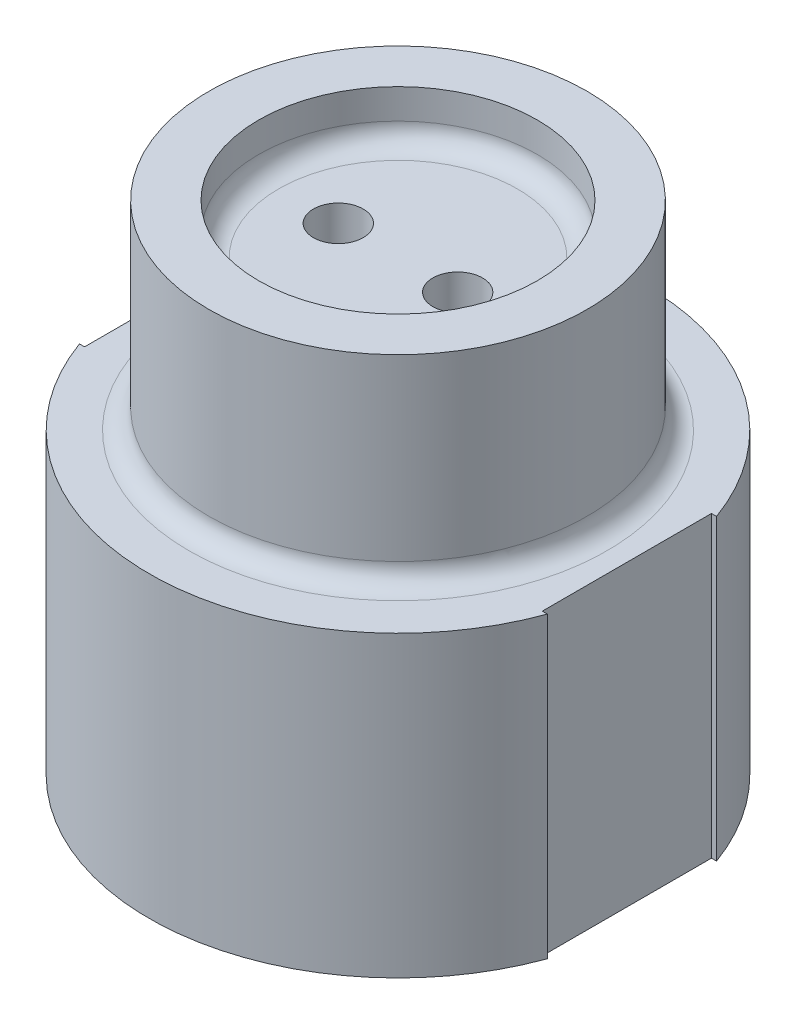
SolidWorks part; units mm, degrees
note: The reader was unsure of these and kept them because the rebuilt part matched: shared geometry of "Sketch4<2>".
ref_plane "Front Plane" through (0, 0, 0) normal (0, 0, 1) x (1, 0, 0)
ref_plane "Top Plane" through (0, 0, 0) normal (0, 1, 0) x (1, 0, 0)
ref_plane "Right Plane" through (0, 0, 0) normal (1, 0, 0) x (0, 0, -1)
sketch "Sketch1" plane through (0, 0, 0) normal (0, 0, 1) x (1, 0, 0)
  line L0 (0, 161.857) -> (0, 0) construction
  line L1 (48.26, 127) -> (48.26, 76.2)
  line L2 (48.26, 76.2) -> (63.5, 76.2)
  line L3 (63.5, 76.2) -> (63.5, 0)
  line L4 (63.5, 0) -> (50.8, 0)
  line L5 (50.8, 12.7) -> (50.8, 63.5)
  line L6 (50.8, 63.5) -> (35.56, 63.5)
  line L7 (35.56, 63.5) -> (35.56, 127)
  line L8 (35.56, 127) -> (48.26, 127)
  line L9 (50.8, 12.7) -> (0, 12.7)
  line L10 (0, 12.7) -> (0, 0)
  line L11 (0, 0) -> (50.8, 0)
  dimension "D1" = 50.8
  dimension "D2" = 76.2
  dimension "D3" = 12.7
  dimension "D4" = 12.7
  dimension "D5" = 50.8
  dimension "D6" = 15.24
  dimension "D7" = 12.7
  dimension "D8" = 12.7
revolve "Revolve1" add sketch "Sketch1" angle 360 about L0
ref_plane "Plane1" through (0, 114.3, 0) normal (0, 1, 0) x (1, 0, 0)
sketch "Sketch2" plane through (0, 114.3, 0) normal (0, 1, 0) x (1, 0, 0)
  circle A0 centre (0, 0) radius 35.56
  circle A1 centre (0, 0) radius 35.56 construction
extrude "Boss-Extrude1" add sketch "Sketch2" against normal blind 7.62
sketch "Sketch3" plane through (0, 0, 0) normal (0, 0, 1) x (1, 0, 0)
  line L0 (0, -25.3664) -> (0, 143.0471) construction
  line L1 (15.24, 114.3) -> (15.24, 50.8)
  line L2 (53.086, 114.3) -> (-53.086, 114.3) construction
  line L3 (15.24, 50.8) -> (33.02, 50.8)
  line L4 (33.02, 50.8) -> (33.02, 0)
  line L5 (-63.5, 0) -> (63.5, 0) construction
  line L6 (-33.02, 50.8) -> (-33.02, 0)
  line L7 (-15.24, 50.8) -> (-33.02, 50.8)
  line L8 (-15.24, 114.3) -> (-15.24, 50.8)
  dimension "D1" = 15.24
  dimension "D2" = 63.5
  dimension "D3" = 17.78
sketch "Sketch4" plane through (0, 114.3, 0) normal (0, 1, 0) x (1, 0, 0)
  line L0 (15.24, 0) -> (33.02, 0) construction
  circle A0 centre (15.24, 0) radius 6.35
  dimension "D1" = 12.7
  dimension "D2" = 15.24
sweep "Sweep-Thin1" add profiles "Sketch4" path "Sketch3" parameters "D1"=2.54
mirror "Mirror1" about plane through (0, 0, 0) normal (1, 0, 0) of "Sweep-Thin1"
extrude "Cut-Extrude1" cut sketch "Sketch4<2>" against normal blind 7.62
sketch "Sketch4<2>" plane through (0, 114.3, 0) normal (0, 1, 0) x (1, 0, 0) same geometry as "Sketch4"
mirror "Mirror2" about plane through (0, 0, 0) normal (1, 0, 0) of "Cut-Extrude1"
sketch "Sketch5" plane through (0, 0, 0) normal (0, -1, 0) x (1, 0, 0)
  line L0 (-58.42, -21.59) -> (-58.42, 21.59)
  line L1 (-58.42, 21.59) -> (-59.717, 21.59)
  line L2 (-58.42, -21.59) -> (-59.717, -21.59)
  arc A0 (-59.717, 21.59) -> (-59.717, -21.59) centre (0, 0) ccw
  circle A2 centre (0, 0) radius 63.5 construction
  point P6 (-58.42, 0)
  dimension "D1" = 43.18
  dimension "D2" = 58.42
extrude "Cut-Extrude2" cut sketch "Sketch5" against normal through all
mirror "Mirror3" about plane through (0, 0, 0) normal (1, 0, 0) of "Cut-Extrude2"
sketch "Sketch6" plane through (0, 12.7, 0) normal (0, 1, 0) x (1, 0, 0)
  circle A0 centre (-33.02, 0) radius 6.35
  circle A1 centre (-33.02, 0) radius 6.35 construction
extrude "Cut-Extrude3" cut sketch "Sketch6" against normal through all
mirror "Mirror4" about plane through (0, 0, 0) normal (1, 0, 0) of "Cut-Extrude3"
fillet "Fillet1" radius 5.08 2 edges at (0, 114.3, 35.56) (0, 76.2, 48.26)
